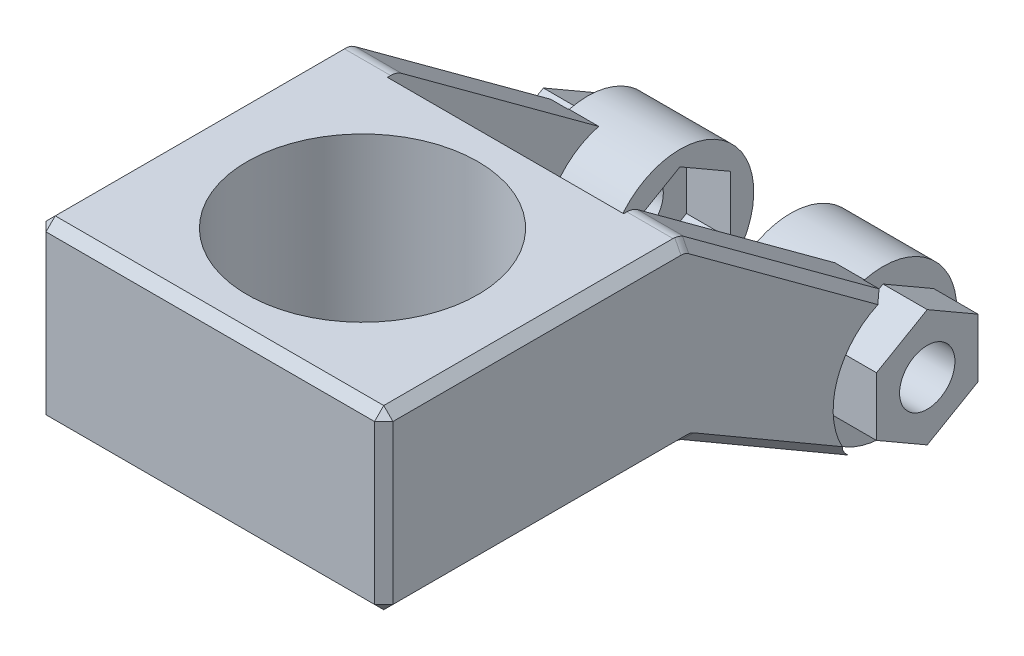
SolidWorks part; units mm, degrees
ref_plane "Front Plane" through (0, 0, 0) normal (0, 0, 1) x (1, 0, 0)
ref_plane "Top Plane" through (0, 0, 0) normal (0, 1, 0) x (1, 0, 0)
ref_plane "Right Plane" through (0, 0, 0) normal (1, 0, 0) x (0, 0, -1)
sketch "Sketch1" plane through (0, 0, 0) normal (0, 1, 0) x (1, 0, 0)
  line L0 (-9.4, 13.1461) -> (-9.4, -15.9532) construction
  line L1 (-19.9267, 0) -> (20.4407, 0) construction
  line L2 (-8.1549, 15.4287) -> (-8.1549, -9.8751) construction
  line L3 (0, -6.25) -> (-8.1549, -6.25) construction
  line L4 (-8.1549, -6.25) -> (-10.7947, -0.8827) construction
  line L5 (0, 6.25) -> (-8.1549, 6.25) construction
  line L6 (-8.1549, 6.25) -> (-10.7947, 0.8827) construction
  line L7 (0, 8.25) -> (-9.4, 8.25)
  line L9 (0, -8.25) -> (-9.4, -8.25)
  line L11 (0, 8.25) -> (0, 6.25)
  line L12 (0, -8.25) -> (0, -6.25)
  line L13 (-9.4, -8.25) -> (-12.5894, -1.7654) construction
  line L14 (-9.4, 8.25) -> (-12.5894, 1.7654) construction
  line L15 (-9.4, -8.25) -> (-9.4, 8.25)
  circle A0 centre (0, 0) radius 6.25 construction
  circle A2 centre (-9, 0) radius 2 construction
  circle A3 centre (-9, 0) radius 4 construction
  arc A5 (0, 6.25) -> (0, -6.25) centre (0, 0) ccw
  dimension "D1" = 12.5
  dimension "D5" = 4
  dimension "D2" = 9.4
  dimension "D3" = 9
  dimension "D7" = 2
  dimension "D8" = 2
  dimension "D9" = 2
extrude "Bracket" add sketch "Sketch1" along normal blind 0.1
ref_plane "Arm Plane" through (-6.4, 0, 0) normal (1, 0, 0) x (0, 0, -1)
sketch "Sketch2" plane through (-6.4, 0, 0) normal (1, 0, 0) x (0, 0, -1)
  line L1 (-8.25, 0) -> (18.1909, -15.3588)
  line L2 (8.25, 0) -> (19.2, -8.027)
  line L5 (-8.25, 0) -> (8.25, 0)
  circle A0 centre (20.2, -11.9) radius 4 construction
  arc A1 (18.1909, -15.3588) -> (19.2, -8.027) centre (20.2, -11.9) ccw
  circle A2 centre (20.2, -11.9) radius 1.5
  dimension "D1" = 8
  dimension "D4" = 3
  dimension "D2" = 20.2
  dimension "D3" = 11.9
  dimension "D5" = 1
extrude "Arm" add sketch "Sketch2" against normal blind 1.6
sketch "Sketch4" plane through (-8, 0, 0) normal (-1, 0, 0) x (0, 0, 1)
  circle A0 centre (-20.2, -11.9) radius 4
  circle A1 centre (-20.2, -11.9) radius 1.5
  circle A2 centre (-20.2, -11.9) radius 1.5 construction
  arc A3 (-19.2, -8.027) -> (-18.1909, -15.3588) centre (-20.2, -11.9) ccw construction
extrude "Effector Mount" add sketch "Sketch4" against normal blind 5
sketch "Sketch5" plane through (-3, 0, 0) normal (1, 0, 0) x (0, 0, -1)
  line L1 (20.2, -8.7246) -> (17.45, -10.3123)
  line L2 (17.45, -10.3123) -> (17.45, -13.4877)
  line L3 (17.45, -13.4877) -> (20.2, -15.0754)
  line L4 (20.2, -15.0754) -> (22.95, -13.4877)
  line L5 (22.95, -13.4877) -> (22.95, -10.3123)
  line L6 (22.95, -10.3123) -> (20.2, -8.7246)
  circle A0 centre (20.2, -11.9) radius 2.75 construction
  dimension "D1" = 5.5
extrude "Mount Trap" cut sketch "Sketch5" against normal blind 2.4
sketch "Sketch6" plane through (-8, 0, 0) normal (-1, 0, 0) x (0, 0, 1)
  line L1 (-17.45, -10.3123) -> (-20.2, -8.7246)
  line L2 (-20.2, -8.7246) -> (-22.95, -10.3123)
  line L3 (-22.95, -10.3123) -> (-22.95, -13.4877)
  line L4 (-22.95, -13.4877) -> (-20.2, -15.0754)
  line L5 (-20.2, -15.0754) -> (-17.45, -13.4877)
  line L6 (-17.45, -13.4877) -> (-17.45, -10.3123)
  circle A0 centre (-20.2, -11.9) radius 2.75 construction
  circle A1 centre (-20.2, -11.9) radius 1.5
  circle A2 centre (-20.2, -11.9) radius 1.5 construction
  dimension "D1" = 5.5
extrude "Mount Adaptor" add sketch "Sketch6" along normal blind 2.4
sketch "Sketch7" plane through (-8, 0, 0) normal (-1, 0, 0) x (0, 0, 1)
  line L0 (-8.25, 0) -> (-19.0966, -7.9513)
  line L1 (-19.2, -8.027) -> (-8.25, 0) construction
  line L2 (8.25, 0) -> (-17.4126, -14.9068)
  line L3 (8.25, 0) -> (-18.1909, -15.3588) construction
  line L4 (-8.25, 0) -> (8.25, 0)
  line L5 (8.25, 0.1) -> (8.25, 0) construction
  circle A0 centre (-20.2, -11.9) radius 4.1 construction
  arc A1 (-19.0966, -7.9513) -> (-17.4126, -14.9068) centre (-20.2, -11.9) cw
  dimension "D1" = 8.2
extrude "Arm Support" add sketch "Sketch7" along normal blind 1.4
sketch "Sketch9" plane through (0, 0, 0) normal (0, -1, 0) x (1, 0, 0)
  line L5 (-6.4, 8.25) -> (-9.4, 8.25)
  line L6 (-9.4, 8.25) -> (-9.4, -8.25)
  line L7 (-9.4, -17.4126) -> (-9.4, 8.25) construction
  line L8 (-6.4, -8.25) -> (-9.4, -8.25)
  line L10 (-6.4, 8.25) -> (-6.4, -8.25)
  line L11 (-6.4, -8.25) -> (0, -8.25)
  line L12 (0, -8.25) -> (0, -6.25)
  line L13 (0, 6.25) -> (0, 8.25)
  line L14 (0, 8.25) -> (-6.4, 8.25)
  line L16 (-6.4, -8.25) -> (0, -8.25)
  line L17 (0, -8.25) -> (0, -6.25)
  line L18 (0, 6.25) -> (0, 8.25)
  line L19 (0, 8.25) -> (-6.4, 8.25)
  arc A2 (0, 6.25) -> (0, -6.25) centre (0, 0) ccw
  arc A3 (0, 6.25) -> (0, -6.25) centre (0, 0) ccw
  dimension "D1" = 0
extrude "Boss-Extrude1" add sketch "Sketch9" along normal blind 9.5844
mirror "Mirror8" about plane through (0, 0, 0) normal (1, 0, 0) of "Boss-Extrude1", "Arm Support", "Mount Adaptor", "Mount Trap", "Effector Mount", "Arm", "Bracket"
sketch "Sketch13" plane through (9.4, 0, 0) normal (1, 0, 0) x (0, 0, -1)
  line L1 (-8.25, 0.1) -> (8.25, 0.1)
  line L2 (-8.25, 0.1) -> (-8.25, 0)
  line L3 (-8.25, 0) -> (8.25, 0)
  line L4 (8.25, 0.1) -> (8.25, 0)
extrude "Cut-Extrude2" cut sketch "Sketch13" against normal through all
chamfer "Chamfer8" distance 0.5 angle 45 13 edges at (-9.4, -12.2456, -12.8313) (-9.4, -9.5844, 0) (-9.4, -4.7922, 8.25) (0, -9.5844, 8.25) (-9.4, -3.9756, -13.6733) (-9.4, 0, 0) (0, 0, 8.25) (9.4, -12.2456, -12.8313) (9.4, -9.5844, 0) (9.4, -4.7922, 8.25) (9.4, -3.9756, -13.6733) (9.4, 0, 0) (0, 0, -8.25)
chamfer "Chamfer9" distance 0.5 angle 45 1 edges at (0, -9.5844, -8.25)
sketch "Sketch14" plane through (6.4, 0, 0) normal (-1, 0, 0) x (0, 0, 1)
  line L0 (-7.75, -9.5844) -> (-8.25, -9.5844)
  line L1 (-8.25, -9.5844) -> (-17.4126, -14.9068) construction
  line L2 (-8.25, -9.5844) -> (-7.9337, -9.4007)
  line L3 (-7.9337, -9.4007) -> (-7.75, -9.5844)
extrude "Boss-Extrude3" add sketch "Sketch14" against normal up to surface (15.4837 mm away) up to face at (9.0973, -9.3871, -2.8031)
sketch "Sketch15" plane through (-6.4, 0, 0) normal (1, 0, 0) x (0, 0, -1)
  line L0 (8.25, -9.5844) -> (7.75, -9.5844)
  line L1 (7.9337, -9.4007) -> (18.1909, -15.3588) construction
  line L2 (7.75, -9.5844) -> (7.9337, -9.4007)
  line L3 (7.9337, -9.4007) -> (8.25, -9.5844)
  line L4 (8.25, -9.5844) -> (-7.75, -9.5844) construction
extrude "Boss-Extrude4" add sketch "Sketch15" against normal up to surface (2.6837 mm away) up to face at (-9.0973, -9.3871, -2.8031)
fillet "Fillet2" radius 1 8 edges at (9.15, -0.25, -8.1682) (-9.15, -0.25, -8.1682) (-7.65, 0, -8.25) (7.65, 0, -8.25) (7.65, -9.5844, -8.25) (9.15, -9.3344, -8.3173) (-9.15, -9.3344, -8.3173) (-7.65, -9.5844, -8.25)
